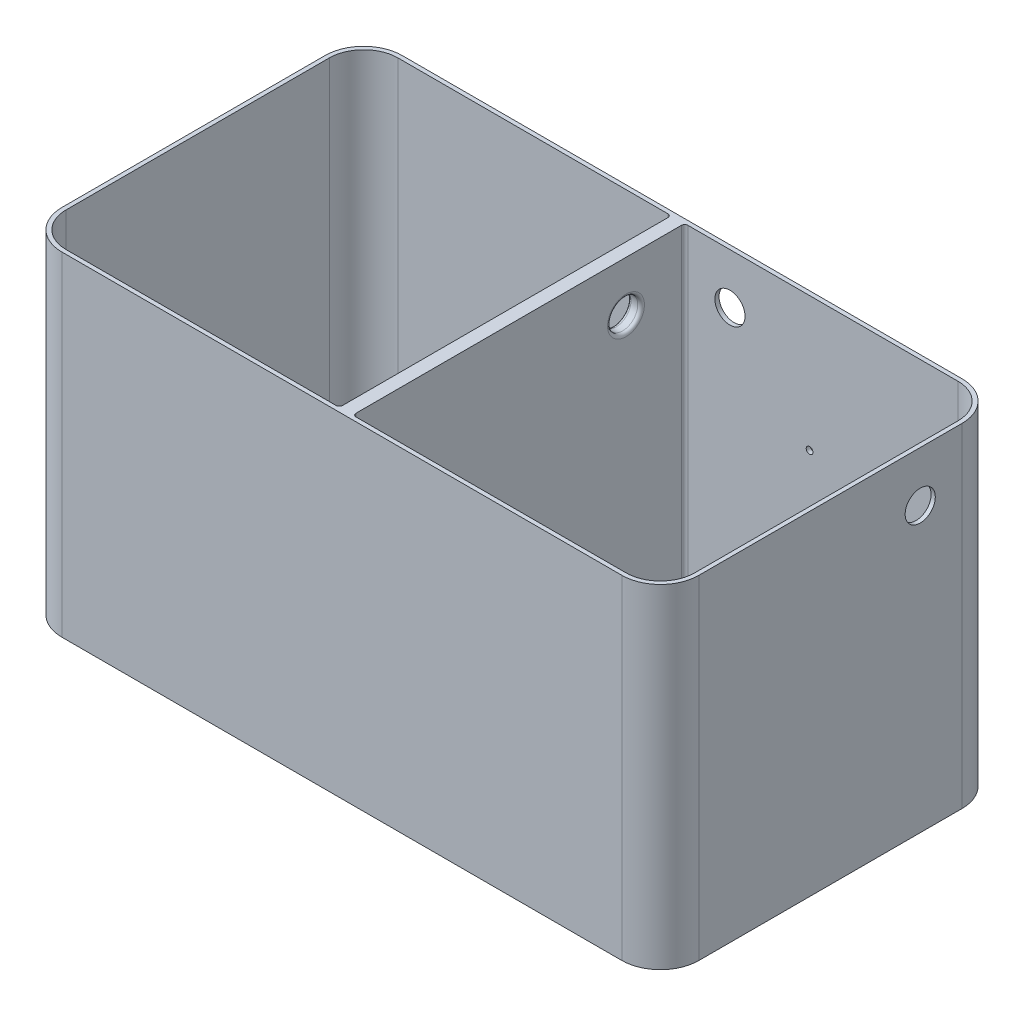
SolidWorks part; units mm, degrees
ref_plane "前视基准面" through (0, 0, 0) normal (0, 0, 1) x (1, 0, 0)
ref_plane "上视基准面" through (0, 0, 0) normal (0, 1, 0) x (1, 0, 0)
ref_plane "右视基准面" through (0, 0, 0) normal (1, 0, 0) x (0, 0, -1)
other "Configuration Table"
sketch "草图1" plane through (0, 0, 0) normal (0, 1, 0) x (1, 0, 0)
  line L1 (-167, 101.5) -> (167, 101.5)
  line L2 (-190, 78.5) -> (-190, -78.5)
  line L3 (-167, -101.5) -> (167, -101.5)
  line L4 (190, 78.5) -> (190, -78.5)
  line L5 (-190, 101.5) -> (190, -101.5) construction
  line L6 (-190, -101.5) -> (190, 101.5) construction
  arc A0 (167, -101.5) -> (190, -78.5) centre (167, -78.5) ccw
  arc A1 (167, 101.5) -> (190, 78.5) centre (167, 78.5) cw
  arc A2 (-190, -78.5) -> (-167, -101.5) centre (-167, -78.5) ccw
  arc A3 (-167, 101.5) -> (-190, 78.5) centre (-167, 78.5) ccw
  point P0 (0, 0)
  dimension "D3" = 23
  dimension "D1" = 380
  dimension "D2" = 203
extrude "凸台-拉伸1" add sketch "草图1" along normal blind 199
sketch "草图3" plane through (0, 199, 0) normal (0, 1, 0) x (1, 0, 0)
  line L0 (-190, 78.5) -> (-190, -78.5) construction
  line L1 (-167, 99) -> (167, 99)
  line L2 (-187.5, 78.5) -> (-187.5, -78.5)
  line L3 (-167, -99) -> (167, -99)
  line L4 (187.5, 78.5) -> (187.5, -78.5)
  line L5 (-187.5, 99) -> (187.5, -99) construction
  line L6 (-187.5, -99) -> (187.5, 99) construction
  line L7 (190, -78.5) -> (190, 78.5) construction
  arc A0 (-187.5, -78.5) -> (-167, -99) centre (-167, -78.5) ccw
  arc A1 (167, -99) -> (187.5, -78.5) centre (167, -78.5) ccw
  arc A2 (167, 99) -> (187.5, 78.5) centre (167, 78.5) cw
  arc A3 (-167, 99) -> (-187.5, 78.5) centre (-167, 78.5) ccw
  point P0 (0, 0)
  dimension "D5" = 20.5
  dimension "D1" = 198
  dimension "D2" = 375
  dimension "D3" = 2.5
  dimension "D4" = 2.5
extrude "切除-拉伸1" cut sketch "草图3" against normal blind 195
sketch "草图4" plane through (0, 4, 0) normal (0, 1, 0) x (1, 0, 0)
  line L0 (0, 99) -> (0, -99) construction
  line L1 (167, 99) -> (-167, 99) construction
  line L2 (-167, -99) -> (167, -99) construction
  line L3 (-4, 99) -> (-4, -99)
  line L4 (-167, -99) -> (167, -99) construction
  line L5 (4, 99) -> (4, -99)
  line L6 (-4, 99) -> (4, 99)
  line L7 (-4, -99) -> (4, -99)
  dimension "D1" = 4
extrude "凸台-拉伸2" add sketch "草图4" along normal blind 195
fillet "圆角1" radius 2 16 edges at (85.5, 4, 99) (181.4957, 4, 92.9957) (187.5, 4, 0) (181.4957, 4, -92.9957) (-85.5, 4, 99) (-181.4957, 4, 92.9957) (-187.5, 4, 0) (-181.4957, 4, -92.9957) (-4, 101.5, -99) (-4, 4, 0) (-4, 101.5, 99) (4, 101.5, 99) (4, 101.5, -99) (4, 4, 0) (85.5, 4, -99) (-85.5, 4, -99)
sketch "草图6" plane through (0, 0, -101.5) normal (0, 0, -1) x (-1, 0, 0)
  line L0 (0, 199) -> (0, 0) construction
  line L1 (-167, 199) -> (167, 199) construction
  line L2 (-6, 199) -> (-6, 0) construction
  line L4 (-167, 0) -> (167, 0) construction
  line L5 (6, 199) -> (6, 0) construction
  line L6 (-167, 199) -> (-167, 0) construction
  circle A0 centre (-155, 119) radius 2
  circle A1 centre (-155, 64) radius 2
  circle A2 centre (-78.5, 64) radius 2
  circle A3 centre (-78.5, 119) radius 2
  circle A4 centre (-31, 169) radius 9
  point P13 (-155, 119)
  point P14 (-155, 64)
  point P17 (-78.5, 119)
  point P18 (-78.5, 64)
  dimension "D5" = 4
  dimension "D6" = 4
  dimension "D7" = 4
  dimension "D8" = 4
  dimension "D10" = 18
  dimension "D1" = 12
  dimension "D2" = 12
  dimension "D3" = 76.5
  dimension "D4" = 55
  dimension "D9" = 80
  dimension "D11" = 25
  dimension "D12" = 30
extrude "切除-拉伸2" cut sketch "草图6" against normal up to next contours A2 | A3 | A0 | A1 | A4
sketch "草图7" plane through (4, 0, 0) normal (1, 0, 0) x (0, 0, -1)
  line L0 (99, 199) -> (99, 0) construction
  line L1 (78.5, 0) -> (101.5, 0) construction
  line L2 (-78.5, 199) -> (78.5, 199) construction
  circle A0 centre (64, 169) radius 9
  dimension "D2" = 18
  dimension "D1" = 35
  dimension "D3" = 30
extrude "切除-拉伸3" cut sketch "草图7" against normal up to next
fillet "圆角2" radius 2 2 edges at (-4, 169, -73) (4, 169, -73)
sketch "草图9" plane through (190, 0, 0) normal (1, 0, 0) x (0, 0, -1)
  line L0 (-78.5, 199) -> (78.5, 199) construction
  line L1 (78.5, 199) -> (78.5, 0) construction
  circle A0 centre (53.5, 169) radius 9
  dimension "D1" = 18
  dimension "D2" = 30
  dimension "D3" = 25
extrude "切除-拉伸4" cut sketch "草图9" against normal up to next
